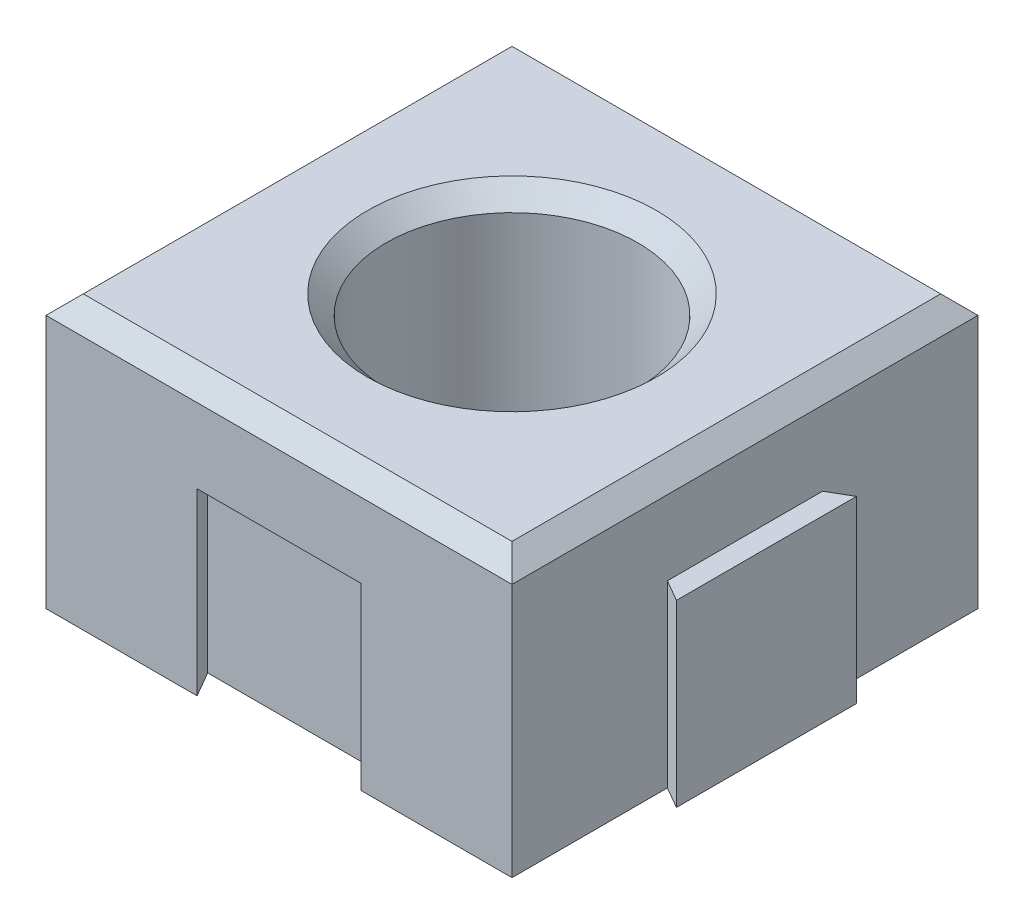
SolidWorks part; units mm, degrees
ref_plane "Front Plane" through (0, 0, 0) normal (0, 0, 1) x (1, 0, 0)
ref_plane "Top Plane" through (0, 0, 0) normal (0, 1, 0) x (1, 0, 0)
ref_plane "Right Plane" through (0, 0, 0) normal (1, 0, 0) x (0, 0, -1)
sketch "Sketch1" plane through (0, 0, 0) normal (0, 1, 0) x (1, 0, 0)
  line L1 (0, 0) -> (50, 0)
  line L2 (0, 0) -> (0, 50)
  line L3 (0, 50) -> (50, 50)
  line L4 (50, 0) -> (50, 50)
  dimension "D1" = 50
extrude "Boss-Extrude1" add sketch "Sketch1" along normal blind 30
sketch "Sketch2" plane through (0, 30, 0) normal (0, 1, 0) x (1, 0, 0)
  line L0 (0, 0) -> (50, 50) construction
  line L1 (0, 50) -> (50, 0) construction
  circle A0 centre (25, 25) radius 13.5
  dimension "D1" = 27
extrude "Cut-Extrude1" cut sketch "Sketch2" against normal blind 26
sketch "Sketch3" plane through (0, 0, 0) normal (0, 1, 0) x (1, 0, 0)
  line L0 (50, 33.5566) -> (52.5, 35) construction
  line L1 (50, 0) -> (50, 50) construction
  line L2 (52.5, 35) -> (52.5, 15) construction
  line L3 (52.5, 15) -> (50, 16.4434) construction
  line L4 (50, 25) -> (52.5, 25) construction
  line L5 (16.4434, 50) -> (15, 52.5) construction
  line L6 (50, 50) -> (0, 50) construction
  line L7 (15, 52.5) -> (35, 52.5) construction
  line L8 (35, 52.5) -> (33.5566, 50) construction
  line L9 (25, 52.5) -> (25, 50) construction
  line L10 (0, 33.5566) -> (2.5, 35) construction
  line L11 (0, 50) -> (0, 0) construction
  line L12 (2.5, 35) -> (2.5, 15) construction
  line L13 (2.5, 15) -> (0, 16.4434) construction
  line L14 (0, 25) -> (2.5, 25) construction
  line L15 (16.4434, 0) -> (15, 2.5) construction
  line L16 (0, 0) -> (50, 0) construction
  line L17 (15, 2.5) -> (35, 2.5) construction
  line L18 (35, 2.5) -> (33.5566, 0) construction
  line L19 (25, 0) -> (25, 2.5) construction
  line L20 (50, 16.6743) -> (50, 33.3257)
  line L21 (33.3257, 50) -> (16.6743, 50)
  line L23 (16.4434, 0) -> (33.5566, 0) construction
  line L24 (50, 33.3257) -> (52.3, 34.6536)
  line L25 (52.3, 34.6536) -> (52.3, 15.3464)
  line L26 (52.3, 15.3464) -> (50, 16.6743)
  line L27 (52.3, 34.6536) -> (52.2, 34.8268) construction
  line L28 (16.2124, 0) -> (14.6536, 2.7)
  line L29 (52.3, 34.6536) -> (52.5, 34.6536) construction
  line L30 (14.6536, 2.7) -> (35.3464, 2.7)
  line L31 (35.3464, 2.7) -> (33.7876, 0)
  line L32 (33.7876, 0) -> (16.2124, 0)
  line L33 (35, 2.5) -> (35, 2.7) construction
  line L34 (35, 2.5) -> (35.1732, 2.4) construction
  line L35 (0, 33.7876) -> (2.7, 35.3464)
  line L36 (2.7, 35.3464) -> (2.7, 14.6536)
  line L37 (2.7, 14.6536) -> (0, 16.2124)
  line L38 (0, 16.2124) -> (0, 33.7876)
  line L39 (2.4, 14.8268) -> (2.5, 15) construction
  line L40 (2.5, 15) -> (2.7, 15) construction
  line L41 (16.6743, 50) -> (15.3464, 52.3)
  line L42 (15.3464, 52.3) -> (34.6536, 52.3)
  line L43 (34.6536, 52.3) -> (33.3257, 50)
  line L44 (15.3464, 52.5) -> (15.3464, 52.3) construction
  line L45 (15.1732, 52.2) -> (15.3464, 52.3) construction
  point P8 (50, 25)
  point P39 (52.3, 25)
  point P40 (25, 0)
  point P53 (0, 25)
  point P59 (25, 52.3)
  point P61 (51.9996, 34.4222)
  point P63 (25, 50)
  dimension "D1" = 0.2
  dimension "D2" = 60
  dimension "D3" = 2.5
  dimension "D4" = 20
extrude "Boss-Extrude2" add sketch "Sketch3" along normal blind 20 contours L20 L24 L25 L26
extrude "Boss-Extrude3" add sketch "Sketch3<3>" along normal blind 20 contours L21 L41 L42 L43
sketch "Sketch3<3>" plane through (0, 0, 0) normal (0, 1, 0) x (1, 0, 0) same geometry as "Sketch3"
extrude "Cut-Extrude5" cut sketch "Sketch3<6>" along normal blind 20 contours L38 L35 L36 L37
sketch "Sketch3<6>" plane through (0, 0, 0) normal (0, 1, 0) x (1, 0, 0) same geometry as "Sketch3"
extrude "Cut-Extrude6" cut sketch "Sketch3<7>" along normal blind 20 contours L32 L28 L30 L31
sketch "Sketch3<7>" plane through (0, 0, 0) normal (0, 1, 0) x (1, 0, 0) same geometry as "Sketch3"
chamfer "Chamfer1" distance 2 angle 45 5 edges at (25, 30, -50) (50, 30, -25) (25, 30, 0) (0, 30, -25) (25, 30, -11.5)
sketch "Sketch4" plane through (0, 0, 0) normal (0, 1, 0) x (1, 0, 0)
  line L0 (12.5, 12.5) -> (37.5, 37.5) construction
  line L1 (12.5, 12.5) -> (37.5, 12.5) construction
  line L2 (12.5, 12.5) -> (12.5, 37.5) construction
  line L3 (12.5, 37.5) -> (37.5, 37.5) construction
  line L4 (37.5, 12.5) -> (37.5, 37.5) construction
  line L5 (12.5, 37.5) -> (37.5, 12.5) construction
  line L6 (0, 0) -> (12.5, 12.5) construction
  line L7 (12.5, 37.5) -> (0, 50) construction
  line L8 (50, 50) -> (37.5, 37.5) construction
  line L9 (50, 0) -> (37.5, 12.5) construction
  line L10 (0, 25) -> (25, 25) construction
  circle A0 centre (12.5, 37.5) radius 3.1
  circle A1 centre (37.5, 37.5) radius 3.1
  circle A2 centre (37.5, 12.5) radius 3.1
  circle A3 centre (12.5, 12.5) radius 3.1
  point P15 (12.5, 25)
  dimension "D1" = 6.2
extrude "Cut-Extrude4" cut sketch "Sketch4" along normal blind 4
chamfer "Chamfer2" distance 1 angle 45 4 edges at (37.5, 4, -9.4) (12.5, 4, -9.4) (12.5, 4, -34.4) (37.5, 4, -34.4)
chamfer "Chamfer3" distance 0.75 angle 45 24 edges at (41.8938, 0, 0) (50, 0, -8.3372) (50, 0, -41.6628) (41.6628, 0, -50) (8.3372, 0, -50) (0, 0, -41.8938) (0, 0, -8.1062) (8.1062, 0, 0) (12.5, 0, -34.4) (37.5, 0, -34.4) (37.5, 0, -9.4) (12.5, 0, -9.4) (51.15, 0, -16.0104) (52.3, 0, -25) (51.15, 0, -33.9896) (33.9896, 0, -51.15) (25, 0, -52.3) (16.0104, 0, -51.15) (1.35, 0, -34.567) (2.7, 0, -25) (1.35, 0, -15.433) (15.433, 0, -1.35) (25, 0, -2.7) (34.567, 0, -1.35)
